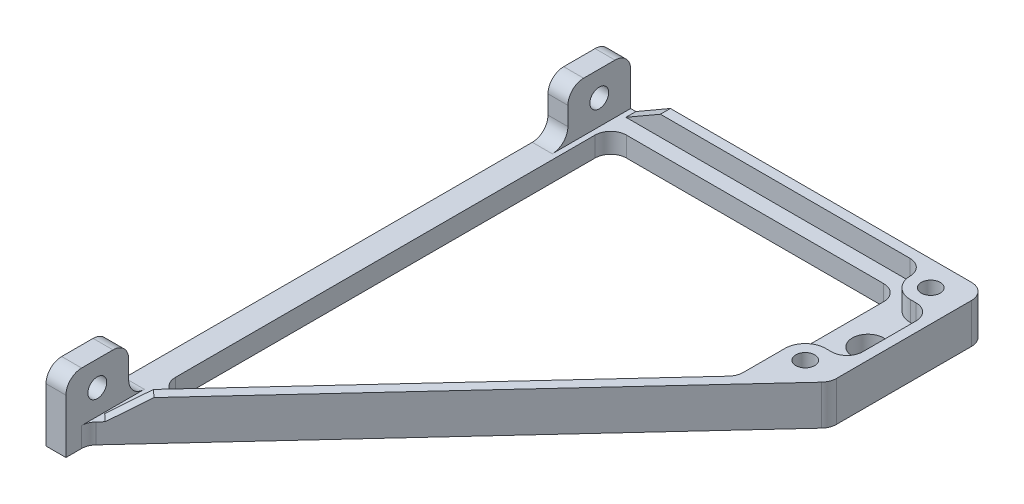
SolidWorks part; units mm, degrees
ref_plane "Front Plane" through (0, 0, 0) normal (0, 0, 1) x (1, 0, 0)
ref_plane "Top Plane" through (0, 0, 0) normal (0, 1, 0) x (1, 0, 0)
ref_plane "Right Plane" through (0, 0, 0) normal (1, 0, 0) x (0, 0, -1)
sketch "Sketch1" plane through (0, 0, 0) normal (0, 1, 0) x (1, 0, 0)
  line L0 (0, 0) -> (120, 0)
  line L1 (120, 0) -> (120, -50)
  line L2 (120, -50) -> (6.35, -173.1208)
  line L3 (0, -180) -> (0, 0)
  line L4 (110, 0) -> (110, -60.8333) construction
  line L5 (0, -180) -> (6.35, -180)
  line L6 (6.35, -180) -> (6.35, -173.1208)
  line L7 (6.35, -173.1208) -> (0, -180) construction
  dimension "D1" = 50
  dimension "D2" = 110
  dimension "D3" = 10
  dimension "D4" = 180
  dimension "D5" = 6.35
extrude "Boss-Extrude1" add sketch "Sketch1" along normal blind 6.35
sketch "Sketch2" plane through (0, 6.35, 0) normal (0, 1, 0) x (1, 0, 0)
  line L0 (110, -8) -> (110, -48) construction
  line L1 (100, -8) -> (100, -59.8721)
  line L2 (100, -8) -> (8, -8)
  line L3 (8, -8) -> (8, -159.5388)
  line L4 (8, -159.5388) -> (100, -59.8721)
  line L7 (0, 0) -> (0, -180)
  line L8 (0, -180) -> (6.35, -180)
  line L9 (6.35, -180) -> (6.35, -173.1208)
  line L10 (6.35, -173.1208) -> (120, -50)
  line L11 (120, -50) -> (120, 0)
  line L12 (120, 0) -> (0, 0)
  line L13 (0, 0) -> (0, -180)
  line L14 (0, -180) -> (6.35, -180)
  line L15 (6.35, -180) -> (6.35, -173.1208)
  line L16 (6.35, -173.1208) -> (120, -50)
  line L17 (120, -50) -> (120, 0)
  line L18 (120, 0) -> (0, 0)
  circle A0 centre (110, -8) radius 3
  circle A1 centre (110, -48) radius 3
  dimension "D4" = 6
  dimension "D1" = 40
  dimension "D2" = 110
  dimension "D3" = 8
  dimension "D6" = 8
  dimension "D7" = 8
  dimension "D8" = 8
  dimension "D5" = 0
extrude "Cut-Extrude3" cut sketch "Sketch2" against normal through all contours L1 L4 L3 L2 | A0 | A1
sketch "Sketch7" plane through (0, 6.35, 0) normal (0, 1, 0) x (1, 0, 0)
  line L0 (4.017, -170.9673) -> (116.825, -48.7586)
  line L1 (116.825, -48.7586) -> (116.825, -3.175)
  line L2 (116.825, -3.175) -> (4.017, -3.175)
  line L3 (4.017, -170.9673) -> (6.35, -173.1208)
  line L4 (3.175, -176.825) -> (3.175, -176.825)
  line L5 (4.017, -3.175) -> (4.017, 0)
  line L6 (0, 0) -> (0, -180)
  line L7 (0, -180) -> (6.35, -180)
  line L8 (6.35, -180) -> (6.35, -173.1208)
  line L9 (6.35, -173.1208) -> (120, -50)
  line L10 (120, -50) -> (120, 0)
  line L11 (120, 0) -> (0, 0)
  line L12 (0, 0) -> (0, -180)
  line L13 (0, -180) -> (6.35, -180)
  line L14 (6.35, -180) -> (6.35, -173.1208)
  line L15 (6.35, -173.1208) -> (120, -50)
  line L16 (120, -50) -> (120, 0)
  line L17 (120, 0) -> (0, 0)
  line L18 (116.825, -3.175) -> (3.175, -3.175) construction
  line L20 (3.175, -3.175) -> (3.175, -176.825) construction
  line L21 (3.175, -176.825) -> (3.175, -171.8795) construction
  line L22 (3.175, -171.8795) -> (116.825, -48.7586) construction
  point P12 (0, 0)
  line M16 (6.35, -173.1208) -> (120, -50)
  line M17 (120, -50) -> (120, 0)
  line M18 (120, 0) -> (0, 0)
  dimension "D1" = 0
  dimension "D2" = 3.175
extrude "Boss-Extrude3" add sketch "Sketch7" along normal blind 6.35 contours L5 L2 L1 L0 M16 M17 M18 region at (61.9522, 6.35, 111.2764)
chamfer "Chamfer1" distance 15 angle 30 2 edges at (5.1835, 12.7, 172.0441) (4.017, 12.7, 1.5875) first distance on face at (61.5064, 12.7, 56.1496)
sketch "Sketch8" plane through (0, 6.35, 0) normal (0, 1, 0) x (1, 0, 0)
  line L0 (110, -14.5) -> (116.825, -14.5)
  line L1 (116.825, -48.7586) -> (116.825, -3.175) construction
  line L2 (103.5, -8) -> (103.5, -3.175)
  line L3 (116.825, -3.175) -> (8.0185, -3.175) construction
  line L4 (103.5, -3.175) -> (116.825, -3.175)
  line L5 (116.825, -3.175) -> (116.825, -14.5)
  line L6 (110, -41.5) -> (116.825, -41.5)
  line L7 (103.5, -48) -> (103.5, -63.194)
  line L8 (6.7311, -168.027) -> (116.825, -48.7586) construction
  line L9 (116.825, -41.5) -> (116.825, -48.7586)
  line L10 (116.825, -48.7586) -> (103.5, -63.194)
  circle A0 centre (110, -48) radius 3 construction
  circle A1 centre (110, -8) radius 3 construction
  circle A2 centre (110, -48) radius 3
  circle A3 centre (110, -8) radius 3
  arc A4 (103.5, -8) -> (110, -14.5) centre (110, -8) ccw
  arc A5 (110, -41.5) -> (103.5, -48) centre (110, -48) ccw
  dimension "D1" = 3.5
extrude "Boss-Extrude4" add sketch "Sketch8" along normal blind 6.35
sketch "Sketch9" plane through (0, 6.35, 0) normal (0, 1, 0) x (1, 0, 0)
  line L0 (6.35, -180) -> (6.35, -173.1208) construction
  line L1 (0, 0) -> (6.35, 0)
  line L2 (0, 0) -> (0, -20)
  line L3 (0, -20) -> (6.35, -20)
  line L4 (6.35, 0) -> (6.35, -20)
  line L5 (0, -180) -> (6.35, -180)
  line L6 (0, -180) -> (0, -160)
  line L7 (0, -160) -> (6.35, -160)
  line L8 (6.35, -180) -> (6.35, -160)
  dimension "D1" = 20
extrude "Boss-Extrude5" add sketch "Sketch9" along normal blind 15.875
sketch "Sketch10" plane through (6.35, 0, 0) normal (1, 0, 0) x (0, 0, -1)
  line L0 (-20, 22.225) -> (0, 6.35) construction
  line L1 (-180, 22.225) -> (-160, 6.35) construction
  circle A0 centre (-10, 14.2875) radius 3
  circle A1 centre (-170, 14.2875) radius 3
  dimension "D1" = 6
extrude "Cut-Extrude4" cut sketch "Sketch10" against normal blind 110.875
fillet "Fillet3" radius 5 17 edges at (103.5, 9.525, 63.194) (116.825, 9.525, 41.5) (116.825, 9.525, 14.5) (103.5, 9.525, 3.175) (120, 6.35, 0) (120, 6.35, 50) (6.35, 3.175, 173.1208) (8, 3.175, 159.5388) (100, 3.175, 59.8721) (100, 3.175, 8) (8, 3.175, 8) (3.175, 22.225, 180) (3.175, 6.35, 160) (3.175, 22.225, 160) (3.175, 22.225, 0) (3.175, 22.225, 20) (3.175, 6.35, 20)
sketch "Sketch11" plane through (0, 6.35, 0) normal (0, 1, 0) x (1, 0, 0)
  line L0 (110, -8) -> (110, -48) construction
  circle A0 centre (110, -28) radius 5
  dimension "D1" = 10
extrude "Cut-Extrude5" cut sketch "Sketch11" against normal blind 15.875
